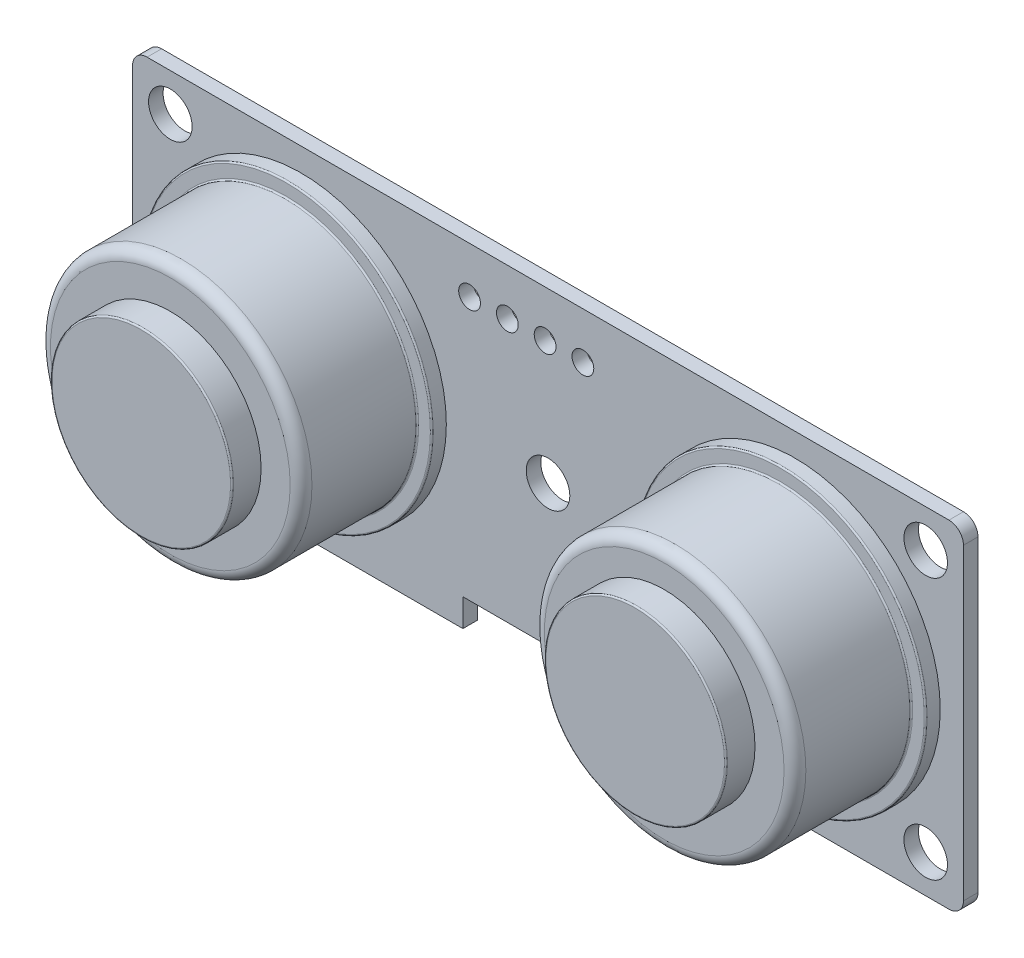
SolidWorks part; units mm, degrees
ref_plane "Ön Düzlem" through (0, 0, 0) normal (0, 0, 1) x (1, 0, 0)
ref_plane "Üst Düzlem" through (0, 0, 0) normal (0, 1, 0) x (1, 0, 0)
ref_plane "Sağ Düzlem" through (0, 0, 0) normal (1, 0, 0) x (0, 0, -1)
sketch "Çizim1" plane through (0, 0, 0) normal (0, 0, 1) x (1, 0, 0)
  line L0 (-5.8595, -11.6) -> (-27.6, -11.6)
  line L1 (27.6, 11.6) -> (-27.6, 11.6)
  line L2 (28.6, 10.6) -> (28.6, -10.6)
  line L3 (27.6, -11.6) -> (5.8595, -11.6)
  line L4 (-28.6, 10.6) -> (-28.6, -10.6)
  line L5 (0, 0) -> (0, -9.6979) construction
  line L6 (0, 0) -> (-28.6, 0) construction
  line L7 (-5.8595, -9.6979) -> (5.8595, -9.6979)
  line L8 (-5.8595, -9.6979) -> (-5.8595, -11.6)
  line L10 (5.8595, -9.6979) -> (5.8595, -11.6)
  line L11 (0, 0) -> (0, 11.6) construction
  line L12 (-26, 9) -> (26, 9) construction
  line L13 (-17.1, 5.1) -> (-17.1, -5.1) construction
  line L14 (-5.4, 8.4) -> (2.6, 8.4) construction
  arc A0 (28.6, -10.6) -> (27.6, -11.6) centre (27.6, -10.6) cw
  arc A1 (27.6, 11.6) -> (28.6, 10.6) centre (27.6, 10.6) cw
  arc A2 (-27.6, -11.6) -> (-28.6, -10.6) centre (-27.6, -10.6) cw
  arc A3 (-27.6, 11.6) -> (-28.6, 10.6) centre (-27.6, 10.6) ccw
  circle A4 centre (-26, 9) radius 1.5
  circle A5 centre (26, 9) radius 1.5
  circle A6 centre (26, -9) radius 1.5
  circle A7 centre (-26, -9) radius 1.5
  circle A8 centre (0, 0) radius 1.5
  circle A9 centre (-17.1, 5.1) radius 0.9
  circle A10 centre (-17.1, -5.1) radius 0.9
  circle A11 centre (17.1, -5.1) radius 0.9
  circle A12 centre (17.1, 5.1) radius 0.9
  circle A13 centre (-5.4, 8.4) radius 0.75
  circle A14 centre (-2.8, 8.4) radius 0.75
  circle A15 centre (-0.2, 8.4) radius 0.75
  circle A16 centre (2.4, 8.4) radius 0.75
  point P1 (0, 5.8)
  point P29 (0, 9)
  dimension "D3" = 1
  dimension "D4" = 3
  dimension "D5" = 52
  dimension "D6" = 3
  dimension "D7" = 6.5
  dimension "D8" = 6.5
  dimension "D9" = 2.6
  dimension "D10" = 2.6
  dimension "D11" = 2.6
  dimension "D12" = 2.6
  dimension "D13" = 18
  dimension "D15" = 1.8
  dimension "D16" = 1.8
  dimension "D20" = 1.5
  dimension "D1" = 57.2
  dimension "D2" = 23.2
  dimension "D14" = 11.5
  dimension "D17" = 8
  dimension "D18" = 3.2
  dimension "D19" = 23.2
  dimension "D21" = 4
extrude "Yükseklik-Ekstrüzyon1" add sketch "Çizim1" along normal blind 1
sketch "Çizim2" plane through (0, 0, 1) normal (0, 0, 1) x (1, 0, 0)
  line L3 (-17, 0) -> (17, 0) construction
  line L4 (0, 1.5) -> (0, -1.5) construction
  circle A0 centre (-17, 0) radius 10
  circle A1 centre (17, 0) radius 10
  circle A2 centre (0, 0) radius 1.5 construction
  point P8 (0, 0)
  dimension "D1" = 20
  dimension "D2" = 34
  dimension "D6" = 20
extrude "Yükseklik-Ekstrüzyon2" add sketch "Çizim2" along normal blind 1 separate body
sketch "Çizim3" plane through (0, 0, 2) normal (0, 0, 1) x (1, 0, 0)
  circle A0 centre (-17, 0) radius 9
  circle A1 centre (17, 0) radius 9
  dimension "D1" = 18
extrude "Yükseklik-Ekstrüzyon3" add sketch "Çizim3" along normal blind 8
sketch "Çizim4" plane through (0, 0, 10) normal (0, 0, 1) x (1, 0, 0)
  circle A0 centre (-17, 0) radius 6.25
  circle A1 centre (17, 0.4139) radius 6.25
  dimension "D1" = 12.5
extrude "Yükseklik-Ekstrüzyon4" add sketch "Çizim4" along normal blind 2 separate body
fillet "Radyus1" radius 0.75 1 edges at (-8, 0, 10)
fillet "Radyus2" radius 0.75 1 edges at (26, 0, 10)
fillet "Radyus3" radius 0.1 1 edges at (-10.75, 0, 12)
fillet "Radyus4" radius 0.1 1 edges at (23.25, 0.4139, 12)
fillet "Radyus5" radius 0.1 2 edges at (-7, 0, 2) (-8, 0, 2)
fillet "Radyus6" radius 0.1 2 edges at (27, 0, 2) (26, 0, 2)
sketch "Çizim10" plane through (0, 0, 0) normal (0, 0, -1) x (-1, 0, 0)
  line L0 (-13.9117, 4.4086) -> (-5.092, 4.4086)
  line L2 (-13.9117, 4.4086) -> (-13.9117, 1.1362)
  line L3 (-13.9117, 1.1362) -> (-5.092, 1.1362)
  line L4 (-5.092, 4.4086) -> (-5.092, 1.1362)
  line L5 (4.9259, -2.3247) -> (9.1781, -2.3247)
  line L6 (4.9259, -2.3247) -> (4.9259, -8.8397)
  line L7 (4.9259, -8.8397) -> (9.1781, -8.8397)
  line L8 (9.1781, -2.3247) -> (9.1781, -8.8397)
  line L21 (-22.8585, 6.7991) -> (-19.9987, 6.7991)
  line L22 (-22.8585, 6.7991) -> (-22.8585, 5.55)
  line L23 (-22.8585, 5.55) -> (-19.9987, 5.55)
  line L24 (-19.9987, 6.7991) -> (-19.9987, 5.55)
  line L54 (-13.9117, 2.7724) -> (-5.092, 2.7724) construction
  line L83 (-21.4286, 5.55) -> (-21.4286, 6.7991) construction
  line L137 (7.052, -2.3247) -> (7.052, -8.8397) construction
  line L180 (11.2809, 9.5742) -> (12.8042, 9.5742)
  line L181 (11.2809, 7.4761) -> (12.8042, 7.4761)
  line L184 (11.2809, 9.5742) -> (11.2809, 7.4761)
  line L185 (12.8042, 9.5742) -> (12.8042, 7.4761)
  line L187 (21.6705, 8.5491) -> (21.6705, 6.4509)
  line L189 (23.1938, 8.5491) -> (23.1938, 6.4509)
  line L192 (21.6705, 8.5491) -> (23.1938, 8.5491)
  line L196 (21.6705, 6.4509) -> (23.1938, 6.4509)
  line L210 (15.5044, 1.6587) -> (15.5044, 2.9078)
  line L212 (12.6446, 1.6587) -> (12.6446, 2.9078)
  line L214 (15.5044, 1.6587) -> (12.6446, 1.6587)
  line L220 (15.5044, 2.9078) -> (12.6446, 2.9078)
  line L222 (14.0745, 2.9078) -> (14.0745, 1.6587) construction
  line L227 (-3.9914, -8.0653) -> (-1.1316, -8.0653)
  line L229 (-3.9914, -6.8162) -> (-1.1316, -6.8162)
  line L236 (-1.1316, -6.8162) -> (-1.1316, -8.0653)
  line L237 (-3.9914, -6.8162) -> (-3.9914, -8.0653)
  line L243 (-2.5615, -8.0653) -> (-2.5615, -6.8162) construction
  line L244 (8.651, 5.9274) -> (8.651, 3.8292)
  line L245 (10.1743, 5.9274) -> (10.1743, 3.8292)
  line L246 (8.651, 3.8292) -> (10.1743, 3.8292)
  line L247 (8.651, 5.9274) -> (10.1743, 5.9274)
  point P92 (-21.4286, 6.8907)
  point P209 (14.0745, 1.5672)
  point P224 (-2.5615, -6.7247)
extrude "Yükseklik-Ekstrüzyon7" add sketch "Çizim10" along normal blind 1
sketch "Çizim11" plane through (0, 0, 0) normal (0, 0, -1) x (-1, 0, 0)
  line L0 (11.2809, 10.1474) -> (12.8042, 10.1474)
  line L1 (11.2809, 10.1474) -> (11.2809, 9.6474)
  line L2 (11.2809, 6.8956) -> (12.8042, 6.8956)
  line L3 (12.8042, 10.1474) -> (12.8042, 9.6474)
  line L4 (-13.7663, 4.4644) -> (-13.7663, 5.8674)
  line L5 (-13.7663, 5.8674) -> (-13.2262, 5.8674)
  line L6 (-13.2262, 4.4644) -> (-13.2262, 5.8674)
  line L7 (-13.7663, 4.4644) -> (-13.2262, 4.4644)
  line L8 (-11.8762, 4.4644) -> (-11.8762, 5.8674)
  line L9 (-12.4163, 5.8674) -> (-11.8762, 5.8674)
  line L10 (-12.4163, 4.4644) -> (-12.4163, 5.8674)
  line L11 (-12.4163, 4.4644) -> (-11.8762, 4.4644)
  line L12 (-10.5262, 4.4644) -> (-10.5262, 5.8674)
  line L13 (-11.0663, 5.8674) -> (-10.5262, 5.8674)
  line L14 (-11.0663, 4.4644) -> (-11.0663, 5.8674)
  line L15 (-11.0663, 4.4644) -> (-10.5262, 4.4644)
  line L16 (-9.1762, 4.4644) -> (-9.1762, 5.8674)
  line L17 (-9.7163, 5.8674) -> (-9.1762, 5.8674)
  line L18 (-9.7163, 4.4644) -> (-9.7163, 5.8674)
  line L19 (-9.7163, 4.4644) -> (-9.1762, 4.4644)
  line L20 (-7.8262, 4.4644) -> (-7.8262, 5.8674)
  line L21 (-8.3663, 5.8674) -> (-7.8262, 5.8674)
  line L22 (-8.3663, 4.4644) -> (-8.3663, 5.8674)
  line L23 (-8.3663, 4.4644) -> (-7.8262, 4.4644)
  line L24 (-6.4762, 4.4644) -> (-6.4762, 5.8674)
  line L25 (-7.0163, 5.8674) -> (-6.4762, 5.8674)
  line L26 (-7.0163, 4.4644) -> (-7.0163, 5.8674)
  line L27 (-7.0163, 4.4644) -> (-6.4762, 4.4644)
  line L28 (-5.1262, 4.4644) -> (-5.1262, 5.8674)
  line L29 (-5.6663, 5.8674) -> (-5.1262, 5.8674)
  line L30 (-5.6663, 4.4644) -> (-5.6663, 5.8674)
  line L31 (-5.6663, 4.4644) -> (-5.1262, 4.4644)
  line L32 (-5.6663, 1.0904) -> (-5.1262, 1.0904)
  line L33 (-5.6663, 1.0904) -> (-5.6663, -0.3126)
  line L34 (-5.6663, -0.3126) -> (-5.1262, -0.3126)
  line L35 (-5.1262, 1.0904) -> (-5.1262, -0.3126)
  line L36 (-7.0163, 1.0904) -> (-6.4762, 1.0904)
  line L37 (-7.0163, 1.0904) -> (-7.0163, -0.3126)
  line L38 (-7.0163, -0.3126) -> (-6.4762, -0.3126)
  line L39 (-6.4762, 1.0904) -> (-6.4762, -0.3126)
  line L40 (-8.3663, 1.0904) -> (-7.8262, 1.0904)
  line L41 (-8.3663, 1.0904) -> (-8.3663, -0.3126)
  line L42 (-8.3663, -0.3126) -> (-7.8262, -0.3126)
  line L43 (-7.8262, 1.0904) -> (-7.8262, -0.3126)
  line L44 (-9.7163, 1.0904) -> (-9.1762, 1.0904)
  line L45 (-9.7163, 1.0904) -> (-9.7163, -0.3126)
  line L46 (-9.7163, -0.3126) -> (-9.1762, -0.3126)
  line L47 (-9.1762, 1.0904) -> (-9.1762, -0.3126)
  line L48 (-11.0663, 1.0904) -> (-10.5262, 1.0904)
  line L49 (-11.0663, 1.0904) -> (-11.0663, -0.3126)
  line L50 (-11.0663, -0.3126) -> (-10.5262, -0.3126)
  line L51 (-10.5262, 1.0904) -> (-10.5262, -0.3126)
  line L52 (-12.4163, 1.0904) -> (-11.8762, 1.0904)
  line L53 (-12.4163, 1.0904) -> (-12.4163, -0.3126)
  line L54 (-12.4163, -0.3126) -> (-11.8762, -0.3126)
  line L55 (-11.8762, 1.0904) -> (-11.8762, -0.3126)
  line L56 (-13.7663, 1.0904) -> (-13.2262, 1.0904)
  line L57 (-13.2262, 1.0904) -> (-13.2262, -0.3126)
  line L58 (-13.7663, -0.3126) -> (-13.2262, -0.3126)
  line L59 (-13.7663, 1.0904) -> (-13.7663, -0.3126)
  line L60 (-22.8585, 5.505) -> (-22.0979, 5.505)
  line L61 (-22.8585, 5.505) -> (-22.8585, 4.6135)
  line L62 (-22.8585, 4.6135) -> (-22.0979, 4.6135)
  line L63 (-22.0979, 5.505) -> (-22.0979, 4.6135)
  line L64 (-19.9987, 4.6135) -> (-20.7593, 4.6135)
  line L65 (-20.7593, 5.505) -> (-20.7593, 4.6135)
  line L66 (-19.9987, 5.505) -> (-20.7593, 5.505)
  line L67 (-19.9987, 5.505) -> (-19.9987, 4.6135)
  line L68 (-21.9148, 6.8541) -> (-20.9424, 6.8541)
  line L69 (-20.9424, 6.8541) -> (-20.9424, 7.6725)
  line L70 (-20.9424, 7.6725) -> (-21.9148, 7.6725)
  line L71 (-21.9148, 6.8541) -> (-21.9148, 7.6725)
  line L72 (3.2713, -2.9897) -> (3.2713, -3.4612)
  line L73 (3.2713, -2.3197) -> (4.8588, -2.3197)
  line L74 (3.2713, -2.3197) -> (3.2713, -2.7912)
  line L75 (3.2713, -2.7912) -> (4.8588, -2.7912)
  line L76 (4.8588, -2.3197) -> (4.8588, -2.7912)
  line L77 (3.2713, -2.9897) -> (4.8588, -2.9897)
  line L78 (4.8588, -2.9897) -> (4.8588, -3.4612)
  line L79 (3.2713, -3.4612) -> (4.8588, -3.4612)
  line L80 (3.2713, -3.6597) -> (3.2713, -4.1312)
  line L81 (3.2713, -3.6597) -> (4.8588, -3.6597)
  line L82 (4.8588, -3.6597) -> (4.8588, -4.1312)
  line L83 (3.2713, -4.1312) -> (4.8588, -4.1312)
  line L84 (3.2713, -4.3297) -> (3.2713, -4.8012)
  line L85 (3.2713, -4.3297) -> (4.8588, -4.3297)
  line L86 (4.8588, -4.3297) -> (4.8588, -4.8012)
  line L87 (3.2713, -4.8012) -> (4.8588, -4.8012)
  line L88 (3.2713, -4.9997) -> (3.2713, -5.4712)
  line L89 (3.2713, -4.9997) -> (4.8588, -4.9997)
  line L90 (4.8588, -4.9997) -> (4.8588, -5.4712)
  line L91 (3.2713, -5.4712) -> (4.8588, -5.4712)
  line L92 (3.2713, -5.6697) -> (3.2713, -6.1412)
  line L93 (3.2713, -5.6697) -> (4.8588, -5.6697)
  line L94 (4.8588, -5.6697) -> (4.8588, -6.1412)
  line L95 (3.2713, -6.1412) -> (4.8588, -6.1412)
  line L96 (3.2713, -6.3397) -> (3.2713, -6.8112)
  line L97 (3.2713, -6.3397) -> (4.8588, -6.3397)
  line L98 (4.8588, -6.3397) -> (4.8588, -6.8112)
  line L99 (3.2713, -6.8112) -> (4.8588, -6.8112)
  line L100 (3.2713, -7.0097) -> (3.2713, -7.4812)
  line L101 (3.2713, -7.0097) -> (4.8588, -7.0097)
  line L102 (4.8588, -7.0097) -> (4.8588, -7.4812)
  line L103 (3.2713, -7.4812) -> (4.8588, -7.4812)
  line L104 (3.2713, -7.6797) -> (3.2713, -8.1512)
  line L105 (3.2713, -7.6797) -> (4.8588, -7.6797)
  line L106 (4.8588, -7.6797) -> (4.8588, -8.1512)
  line L107 (3.2713, -8.1512) -> (4.8588, -8.1512)
  line L108 (3.2713, -8.3497) -> (3.2713, -8.8212)
  line L109 (3.2713, -8.3497) -> (4.8588, -8.3497)
  line L110 (4.8588, -8.3497) -> (4.8588, -8.8212)
  line L111 (3.2713, -8.8212) -> (4.8588, -8.8212)
  line L112 (10.8327, -8.8212) -> (9.2452, -8.8212)
  line L113 (9.2452, -8.3497) -> (9.2452, -8.8212)
  line L114 (10.8327, -8.3497) -> (9.2452, -8.3497)
  line L115 (10.8327, -8.3497) -> (10.8327, -8.8212)
  line L116 (10.8327, -8.1512) -> (9.2452, -8.1512)
  line L117 (9.2452, -7.6797) -> (9.2452, -8.1512)
  line L118 (10.8327, -7.6797) -> (9.2452, -7.6797)
  line L119 (10.8327, -7.6797) -> (10.8327, -8.1512)
  line L120 (10.8327, -7.4812) -> (9.2452, -7.4812)
  line L121 (9.2452, -7.0097) -> (9.2452, -7.4812)
  line L122 (10.8327, -7.0097) -> (9.2452, -7.0097)
  line L123 (10.8327, -7.0097) -> (10.8327, -7.4812)
  line L124 (10.8327, -6.8112) -> (9.2452, -6.8112)
  line L125 (9.2452, -6.3397) -> (9.2452, -6.8112)
  line L126 (10.8327, -6.3397) -> (9.2452, -6.3397)
  line L127 (10.8327, -6.3397) -> (10.8327, -6.8112)
  line L128 (10.8327, -6.1412) -> (9.2452, -6.1412)
  line L129 (9.2452, -5.6697) -> (9.2452, -6.1412)
  line L130 (10.8327, -5.6697) -> (9.2452, -5.6697)
  line L131 (10.8327, -5.6697) -> (10.8327, -6.1412)
  line L132 (10.8327, -5.4712) -> (9.2452, -5.4712)
  line L133 (9.2452, -4.9997) -> (9.2452, -5.4712)
  line L134 (10.8327, -4.9997) -> (9.2452, -4.9997)
  line L135 (10.8327, -4.9997) -> (10.8327, -5.4712)
  line L136 (10.8327, -4.8012) -> (9.2452, -4.8012)
  line L137 (9.2452, -4.3297) -> (9.2452, -4.8012)
  line L138 (10.8327, -4.3297) -> (9.2452, -4.3297)
  line L139 (10.8327, -4.3297) -> (10.8327, -4.8012)
  line L140 (10.8327, -4.1312) -> (9.2452, -4.1312)
  line L141 (9.2452, -3.6597) -> (9.2452, -4.1312)
  line L142 (10.8327, -3.6597) -> (9.2452, -3.6597)
  line L143 (10.8327, -3.6597) -> (10.8327, -4.1312)
  line L144 (10.8327, -3.4612) -> (9.2452, -3.4612)
  line L145 (9.2452, -2.9897) -> (9.2452, -3.4612)
  line L146 (10.8327, -2.9897) -> (9.2452, -2.9897)
  line L147 (9.2452, -2.3197) -> (9.2452, -2.7912)
  line L148 (10.8327, -2.7912) -> (9.2452, -2.7912)
  line L149 (10.8327, -2.3197) -> (10.8327, -2.7912)
  line L150 (10.8327, -2.3197) -> (9.2452, -2.3197)
  line L151 (10.8327, -2.9897) -> (10.8327, -3.4612)
  line L152 (11.2809, 9.6474) -> (12.8042, 9.6474)
  line L153 (11.2809, 7.3956) -> (12.8042, 7.3956)
  line L154 (11.2809, 7.3956) -> (11.2809, 6.8956)
  line L155 (12.8042, 7.3956) -> (12.8042, 6.8956)
  line L156 (23.1938, 9.1223) -> (23.1938, 8.6223)
  line L157 (23.1938, 6.3705) -> (23.1938, 5.8705)
  line L158 (21.6705, 9.1223) -> (21.6705, 8.6223)
  line L159 (21.6705, 8.6223) -> (23.1938, 8.6223)
  line L160 (21.6705, 5.8705) -> (23.1938, 5.8705)
  line L161 (21.6705, 6.3705) -> (21.6705, 5.8705)
  line L162 (21.6705, 6.3705) -> (23.1938, 6.3705)
  line L163 (21.6705, 9.1223) -> (23.1938, 9.1223)
  line L164 (14.7438, 2.9628) -> (14.7438, 3.8543)
  line L165 (12.6446, 2.9628) -> (13.4052, 2.9628)
  line L166 (13.5883, 1.6137) -> (13.5883, 0.7953)
  line L167 (15.5044, 2.9628) -> (15.5044, 3.8543)
  line L168 (15.5044, 2.9628) -> (14.7438, 2.9628)
  line L169 (12.6446, 3.8543) -> (13.4052, 3.8543)
  line L170 (14.5607, 1.6137) -> (14.5607, 0.7953)
  line L171 (13.4052, 2.9628) -> (13.4052, 3.8543)
  line L172 (14.5607, 1.6137) -> (13.5883, 1.6137)
  line L173 (15.5044, 3.8543) -> (14.7438, 3.8543)
  line L174 (12.6446, 2.9628) -> (12.6446, 3.8543)
  line L175 (13.5883, 0.7953) -> (14.5607, 0.7953)
  line L176 (-2.0753, -6.7612) -> (-2.0753, -5.9428)
  line L177 (-1.8922, -8.1103) -> (-1.8922, -9.0018)
  line L178 (-3.2308, -8.1103) -> (-3.2308, -9.0018)
  line L179 (-1.1316, -9.0018) -> (-1.8922, -9.0018)
  line L180 (-3.0477, -6.7612) -> (-2.0753, -6.7612)
  line L181 (-3.9914, -8.1103) -> (-3.9914, -9.0018)
  line L182 (-3.9914, -8.1103) -> (-3.2308, -8.1103)
  line L183 (-3.9914, -9.0018) -> (-3.2308, -9.0018)
  line L184 (-3.0477, -6.7612) -> (-3.0477, -5.9428)
  line L185 (-1.1316, -8.1103) -> (-1.8922, -8.1103)
  line L186 (-1.1316, -8.1103) -> (-1.1316, -9.0018)
  line L187 (-2.0753, -5.9428) -> (-3.0477, -5.9428)
  line L188 (10.1743, 6.5142) -> (10.1743, 6.0142)
  line L189 (8.651, 6.5142) -> (8.651, 6.0142)
  line L190 (8.651, 3.7624) -> (8.651, 3.2624)
  line L191 (10.1743, 3.7624) -> (10.1743, 3.2624)
  line L192 (8.651, 6.0142) -> (10.1743, 6.0142)
  line L193 (8.651, 6.5142) -> (10.1743, 6.5142)
  line L194 (8.651, 3.7624) -> (10.1743, 3.7624)
  line L195 (8.651, 3.2624) -> (10.1743, 3.2624)
extrude "Yükseklik-Ekstrüzyon8" add sketch "Çizim11" along normal blind 1
fillet "Radyus8" radius 0.5 49 edges at (3.6111, -9.0018, -1) (1.5119, -9.0018, -1) (2.5615, -5.9428, -1) (-3.2713, -2.5555, -1) (-3.2713, -3.2255, -1) (-3.2713, -3.8955, -1) (-3.2713, -4.5655, -1) (-3.2713, -5.2355, -1) (-3.2713, -5.9055, -1) (-3.2713, -6.5755, -1) (-3.2713, -7.2455, -1) (-3.2713, -7.9155, -1) (-3.2713, -8.5855, -1) (-10.8327, -8.5855, -1) (-10.8327, -7.9155, -1) (-10.8327, -7.2455, -1) (-10.8327, -6.5755, -1) (-10.8327, -5.9055, -1) (-10.8327, -5.2355, -1) (-10.8327, -4.5655, -1) (-10.8327, -3.8955, -1) (-10.8327, -3.2255, -1) (-10.8327, -2.5555, -1) (-14.0745, 0.7953, -1) (-15.1241, 3.8543, -1) (-13.0249, 3.8543, -1) (-22.4322, 5.8705, -1) (-22.4322, 9.1223, -1) (-12.0425, 6.8956, -1) (-12.0425, 10.1474, -1) (5.3962, -0.3126, -1) (6.7462, -0.3126, -1) (8.0962, -0.3126, -1) (9.4462, -0.3126, -1) (10.7962, -0.3126, -1) (12.1462, -0.3126, -1) (13.4962, -0.3126, -1) (5.3962, 5.8674, -1) (6.7462, 5.8674, -1) (8.0962, 5.8674, -1) (9.4462, 5.8674, -1) (10.7962, 5.8674, -1) (12.1462, 5.8674, -1) (13.4962, 5.8674, -1) (20.379, 4.6135, -1) (22.4782, 4.6135, -1) (21.4286, 7.6725, -1) (-9.4126, 3.2624, -1) (-9.4126, 6.5142, -1)
